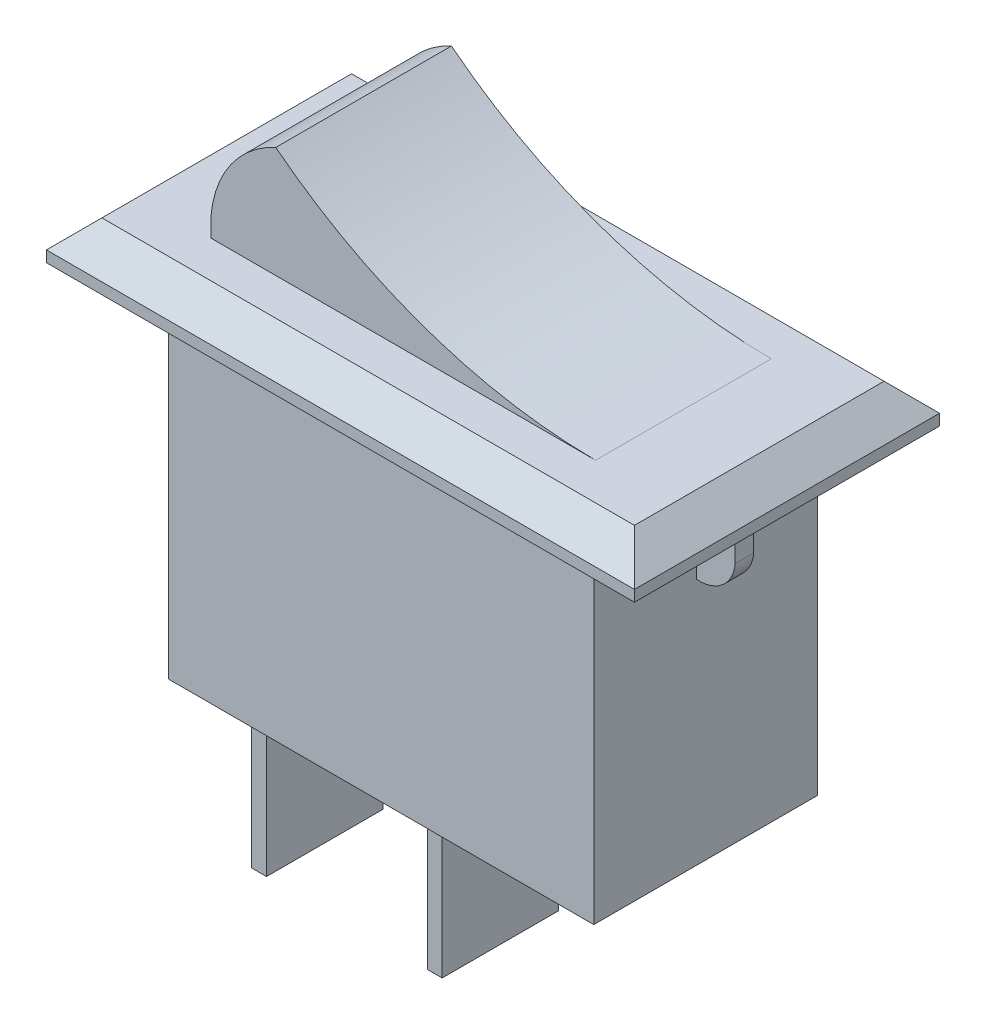
SolidWorks part; units mm, degrees
note: '?' marks a value the reader was unsure of.
ref_plane "Front Plane" through (0, 0, 0) normal (0, 0, 1) x (1, 0, 0)
ref_plane "Top Plane" through (0, 0, 0) normal (0, 1, 0) x (1, 0, 0)
ref_plane "Right Plane" through (0, 0, 0) normal (1, 0, 0) x (0, 0, -1)
sketch "Sketch1" plane through (0, 0, 0) normal (0, 1, 0) x (1, 0, 0)
  line L1 (0, 0) -> (23, 0)
  line L2 (0, 0) -> (0, 12.1)
  line L3 (0, 12.1) -> (23, 12.1)
  line L4 (23, 0) -> (23, 12.1)
  dimension "D1" = 23
  dimension "D2" = 12.1
extrude "Boss-Extrude1" add sketch "Sketch1" along normal blind 18.4
sketch "Sketch2" plane through (0, 0, 0) normal (0, -1, 0) x (1, 0, 0)
  line L0 (0, -12.1) -> (0, 0) construction
  line L1 (1.6, -2.9) -> (2.4, -2.9)
  line L2 (1.6, -2.9) -> (1.6, -9.2)
  line L3 (1.6, -9.2) -> (2.4, -9.2)
  line L4 (2.4, -2.9) -> (2.4, -9.2)
  line L5 (11.1, -2.9) -> (11.9, -2.9)
  line L6 (11.1, -2.9) -> (11.1, -9.2)
  line L7 (11.1, -9.2) -> (11.9, -9.2)
  line L8 (11.9, -2.9) -> (11.9, -9.2)
  line L10 (0, 0) -> (23, 0) construction
  dimension "D1" = 0.8
  dimension "D2" = 0.8
  dimension "D3" = 6.3
  dimension "D4" = 6.3
  dimension "D5" = 8.7
  dimension "D6" = 1.6
  dimension "D7" = 2.9
  dimension "D8" = 2.9
extrude "Boss-Extrude2" add sketch "Sketch2" along normal blind 9.5
sketch "Sketch3" plane through (0, 18.4, 0) normal (0, 1, 0) x (1, 0, 0)
  line L0 (0, 12.1) -> (0, 0) construction
  line L1 (-4.4, -2.2) -> (27.4, -2.2)
  line L2 (-4.4, -2.2) -> (-4.4, 14.3)
  line L3 (-4.4, 14.3) -> (27.4, 14.3)
  line L4 (27.4, -2.2) -> (27.4, 14.3)
  line L5 (23, 12.1) -> (0, 12.1) construction
  dimension "D1" = 16.5
  dimension "D2" = 31.8
  dimension "D3" = 4.4
  dimension "D4" = 2.2
extrude "Boss-Extrude3" add sketch "Sketch3" along normal blind 2.1
chamfer "Chamfer1" distance 1.5 angle 45 4 edges at (11.5, 20.5, -14.3) (27.4, 20.5, -6.05) (11.5, 20.5, 2.2) (-4.4, 20.5, -6.05)
ref_axis "Axis2" through (11.5, 18.4, 0) along (0, -1, 0)?
ref_plane "Plane1" through (11.5, 0, 0) normal (-1, 0, 0) x (0, 0, 1)
sketch "Sketch4" plane through (0, 0, 0) normal (-1, 0, 0) x (0, 0, 1)
  line L0 (-12.1, 18.4) -> (0, 18.4) construction
  line L1 (-6.55, 18.4) -> (-5.55, 18.4)
  line L2 (-6.55, 18.4) -> (-6.55, 13.4)
  line L3 (-6.55, 13.4) -> (-5.55, 13.4)
  line L4 (-5.55, 18.4) -> (-5.55, 13.4)
  line L5 (-12.1, 18.4) -> (-12.1, 0) construction
  dimension "D1" = 5
  dimension "D2" = 1
  dimension "D3" = 5.55
extrude "Boss-Extrude4" add sketch "Sketch4" along normal blind 2.1
sketch "Sketch5" plane through (0, 0, -5.55) normal (0, 0, 1) x (1, 0, 0)
  line L0 (-2.1, 13.4) -> (-2.1, 18.4) construction
  line L1 (-2.1, 15.1877) -> (-2.1, 13.4)
  line L2 (-2.1, 13.4) -> (0, 13.4)
  arc A0 (0, 13.4) -> (-2.1, 15.1877) centre (-0.1562, 15.3438) cw
  line M3 (-2.1, 18.4) -> (-2.1, 13.4)
  line M4 (-2.1, 13.4) -> (0, 13.4)
  dimension "D1" = 1.9501
extrude "Cut-Extrude1" cut sketch "Sketch5" against normal up to surface (1 mm away) contours A0 M4 M3 up to face at (-1.05, 15.9, -6.55)
mirror "Mirror2" about plane through (11.5, 0, 0) normal (-1, 0, 0) of "Boss-Extrude4"
mirror "Mirror3" about plane through (11.5, 0, 0) normal (-1, 0, 0) of "Cut-Extrude1"
sketch "Sketch7" plane through (0, 20.5, 0) normal (0, 1, 0) x (1, 0, 0)
  line L0 (-4.4, -2.2) -> (-4.4, 14.3) construction
  line L1 (1, 10.8) -> (22, 10.8)
  line L2 (1, 10.8) -> (1, 1.3)
  line L3 (1, 1.3) -> (22, 1.3)
  line L4 (22, 10.8) -> (22, 1.3)
  line L5 (-4.4, 14.3) -> (27.4, 14.3) construction
  dimension "D1" = 21
  dimension "D2" = 9.5
  dimension "D3" = 5.4
  dimension "D4" = 3.5
extrude "Boss-Extrude5" add sketch "Sketch7" along normal blind 6
sketch "Sketch8" plane through (0, 0, -1.3) normal (0, 0, 1) x (1, 0, 0)
  line L0 (1, 26.5) -> (22, 26.5) construction
  line L2 (4.5, 26.5) -> (22, 26.5)
  line L3 (22, 26.5) -> (22, 20.5)
  line L4 (1, 20.5) -> (1, 26.5)
  line L5 (1, 26.5) -> (4.5, 26.5)
  arc A0 (1, 20.5) -> (4.5, 26.5) centre (6.9976, 21.0223) cw
  arc A1 (4.5, 26.5) -> (22, 20.5) centre (21.8999, 48.7288) ccw
  line M1 (1, 20.5) -> (22, 20.5)
  line M2 (22, 20.5) -> (22, 26.5)
  line M3 (22, 26.5) -> (1, 26.5)
  line M4 (1, 26.5) -> (1, 20.5)
  dimension "D2" = 28.229
  dimension "D3" = 6.0203
  dimension "D1" = 3.5
extrude "Cut-Extrude3" cut sketch "Sketch8" against normal up to surface (9.5 mm away) contours A0 M4 M3 | A1 M3 M1 M2 up to face at (11.5, 23.5, -10.8)
